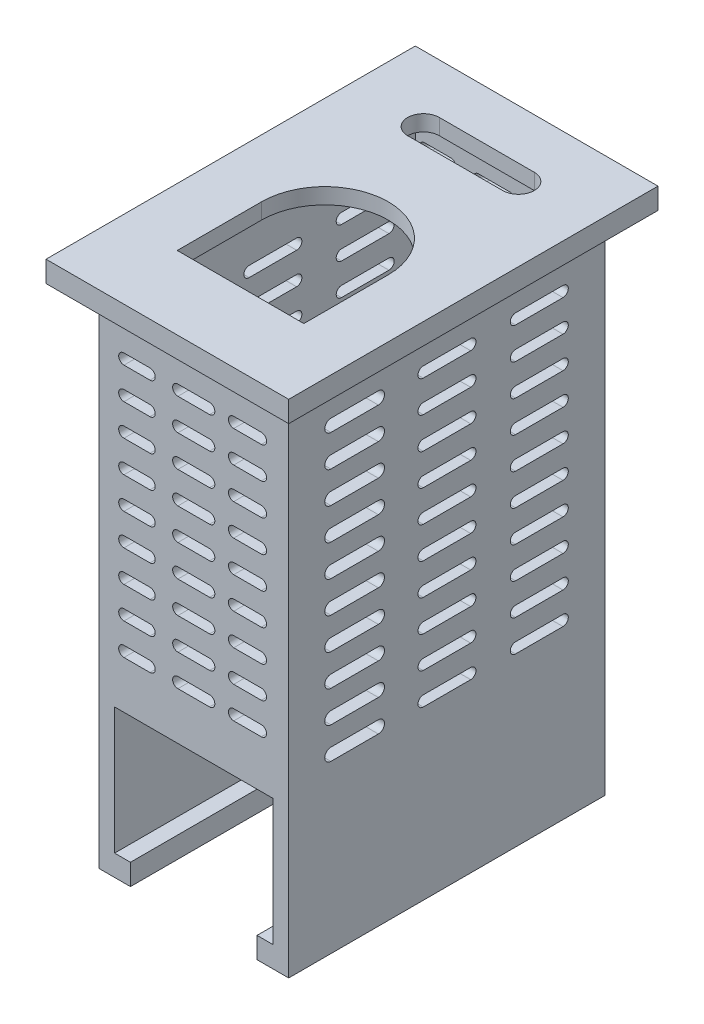
SolidWorks part; units mm, degrees
ref_plane "Front Plane" through (0, 0, 0) normal (0, 0, 1) x (1, 0, 0)
ref_plane "Top Plane" through (0, 0, 0) normal (0, 1, 0) x (1, 0, 0)
ref_plane "Right Plane" through (0, 0, 0) normal (1, 0, 0) x (0, 0, -1)
sketch "Sketch1" plane through (0, 0, 0) normal (0, 0, 1) x (1, 0, 0)
  line L0 (-29.7369, -3.7818) -> (-29.7369, -31.9754) construction
  line L1 (-37.2369, -25.1367) -> (-37.2369, -13.1367)
  line L2 (-38.7369, -29.1367) -> (-20.7369, -29.1367)
  line L3 (-29.7369, -29.1367) -> (-29.7369, -27.1367)
  line L4 (-38.7369, -27.1367) -> (-20.7369, -27.1367)
  line L5 (-20.7369, -29.1367) -> (-20.7369, -27.1367)
  line L6 (-35.7369, -27.1367) -> (-23.7369, -27.1367)
  line L7 (-29.7369, -27.1367) -> (-29.7369, -25.1367)
  line L8 (-35.7369, -25.1367) -> (-23.7369, -25.1367)
  line L9 (-23.7369, -27.1367) -> (-23.7369, -25.1367)
  line L10 (-37.2369, -25.1367) -> (-22.2369, -25.1367)
  line L11 (-29.7369, -25.1367) -> (-29.7369, -13.1367)
  line L12 (-37.2369, -13.1367) -> (-22.2369, -13.1367)
  line L13 (-22.2369, -25.1367) -> (-22.2369, -13.1367)
  line L14 (-35.7369, -27.1367) -> (-35.7369, -25.1367)
  line L15 (-38.7369, -29.1367) -> (-38.7369, -27.1367)
  line L16 (-38.7369, -27.1367) -> (-20.7369, -27.1367)
  line L17 (-38.7369, -27.1367) -> (-38.7369, 20.8633)
  line L18 (-20.7369, -27.1367) -> (-20.7369, 20.8633)
  line L19 (-38.7369, 20.8633) -> (-20.7369, 20.8633)
  line L21 (-41.2369, 20.8633) -> (-18.2369, 20.8633)
  line L22 (-41.2369, 20.8633) -> (-41.2369, 22.8633)
  line L23 (-41.2369, 22.8633) -> (-18.2369, 22.8633)
  line L24 (-18.2369, 20.8633) -> (-18.2369, 22.8633)
  point P24 (0, 0)
  dimension "D1" = 2
  dimension "D2" = 2
  dimension "D3" = 16
  dimension "D4" = 9
  dimension "D5" = 6
  dimension "D6" = 7.5
  dimension "D7" = 50
  dimension "D8" = 2
  dimension "D9" = 2.5
  dimension "D10" = 2.5
extrude "Boss-Extrude1" add sketch "Sketch1" along normal blind 30 contours L19 L17 L4 L14 L10 L1 L12 L13 L9 L18 | L21 L24 L23 L22 L19 region at (-29.7369, 2.0633, 0) region at (-29.7369, 21.8633, 0)
shell "Shell5" thickness 1.5 removed face at (-29.7369, -13.1367, 15)
sketch "Sketch2" plane through (-20.7369, 0, 0) normal (1, 0, 0) x (0, 0, -1)
  line L0 (-30, 22.8633) -> (0, 22.8633) construction
  line L1 (-26, 16.2284) -> (0, 16.2284) construction
  line L2 (0, -27.1367) -> (0, 20.8633) construction
  line L3 (-26, 16.2284) -> (-21.5035, 16.2284) construction
  line L4 (-26, 16.8123) -> (-21.5035, 16.8123)
  line L5 (-26, 15.6445) -> (-21.5035, 15.6445)
  line L6 (-17.2482, 16.2284) -> (-12.7518, 16.2284) construction
  line L7 (-17.2482, 16.7284) -> (-12.7518, 16.7284)
  line L8 (-17.2482, 15.7284) -> (-12.7518, 15.7284)
  line L9 (-8.4965, 16.2119) -> (-4, 16.2119) construction
  line L10 (-8.4965, 16.7119) -> (-4, 16.7119)
  line L11 (-8.4965, 15.7119) -> (-4, 15.7119)
  line L12 (-15, 22.8633) -> (-15, -27.1367) construction
  line L13 (-30, -27.1367) -> (0, -27.1367) construction
  line L14 (-30, -27.1367) -> (-30, 20.8633) construction
  line L15 (-26, 13.2284) -> (-21.5035, 13.2284) construction
  line L16 (-26, 13.8123) -> (-21.5035, 13.8123)
  line L17 (-26, 12.6445) -> (-21.5035, 12.6445)
  line L18 (-17.2482, 13.2284) -> (-12.7518, 13.2284) construction
  line L19 (-17.2482, 13.7284) -> (-12.7518, 13.7284)
  line L20 (-17.2482, 12.7284) -> (-12.7518, 12.7284)
  line L21 (-8.4965, 13.2119) -> (-4, 13.2119) construction
  line L22 (-8.4965, 13.7119) -> (-4, 13.7119)
  line L23 (-8.4965, 12.7119) -> (-4, 12.7119)
  line L24 (-26, 10.2284) -> (-21.5035, 10.2284) construction
  line L25 (-26, 10.8123) -> (-21.5035, 10.8123)
  line L26 (-26, 9.6445) -> (-21.5035, 9.6445)
  line L27 (-17.2482, 10.2284) -> (-12.7518, 10.2284) construction
  line L28 (-17.2482, 10.7284) -> (-12.7518, 10.7284)
  line L29 (-17.2482, 9.7284) -> (-12.7518, 9.7284)
  line L30 (-8.4965, 10.2119) -> (-4, 10.2119) construction
  line L31 (-8.4965, 10.7119) -> (-4, 10.7119)
  line L32 (-8.4965, 9.7119) -> (-4, 9.7119)
  line L33 (-26, 7.2284) -> (-21.5035, 7.2284) construction
  line L34 (-26, 7.8123) -> (-21.5035, 7.8123)
  line L35 (-26, 6.6445) -> (-21.5035, 6.6445)
  line L36 (-17.2482, 7.2284) -> (-12.7518, 7.2284) construction
  line L37 (-17.2482, 7.7284) -> (-12.7518, 7.7284)
  line L38 (-17.2482, 6.7284) -> (-12.7518, 6.7284)
  line L39 (-8.4965, 7.2119) -> (-4, 7.2119) construction
  line L40 (-8.4965, 7.7119) -> (-4, 7.7119)
  line L41 (-8.4965, 6.7119) -> (-4, 6.7119)
  line L42 (-26, 4.2284) -> (-21.5035, 4.2284) construction
  line L43 (-26, 4.8123) -> (-21.5035, 4.8123)
  line L44 (-26, 3.6445) -> (-21.5035, 3.6445)
  line L45 (-17.2482, 4.2284) -> (-12.7518, 4.2284) construction
  line L46 (-17.2482, 4.7284) -> (-12.7518, 4.7284)
  line L47 (-17.2482, 3.7284) -> (-12.7518, 3.7284)
  line L48 (-8.4965, 4.2119) -> (-4, 4.2119) construction
  line L49 (-8.4965, 4.7119) -> (-4, 4.7119)
  line L50 (-8.4965, 3.7119) -> (-4, 3.7119)
  line L51 (-26, 1.2284) -> (-21.5035, 1.2284) construction
  line L52 (-26, 1.8123) -> (-21.5035, 1.8123)
  line L53 (-26, 0.6445) -> (-21.5035, 0.6445)
  line L54 (-17.2482, 1.2284) -> (-12.7518, 1.2284) construction
  line L55 (-17.2482, 1.7284) -> (-12.7518, 1.7284)
  line L56 (-17.2482, 0.7284) -> (-12.7518, 0.7284)
  line L57 (-8.4965, 1.2119) -> (-4, 1.2119) construction
  line L58 (-8.4965, 1.7119) -> (-4, 1.7119)
  line L59 (-8.4965, 0.7119) -> (-4, 0.7119)
  line L60 (-26, -1.7716) -> (-21.5035, -1.7716) construction
  line L61 (-26, -1.1877) -> (-21.5035, -1.1877)
  line L62 (-26, -2.3555) -> (-21.5035, -2.3555)
  line L63 (-17.2482, -1.7716) -> (-12.7518, -1.7716) construction
  line L64 (-17.2482, -1.2716) -> (-12.7518, -1.2716)
  line L65 (-17.2482, -2.2716) -> (-12.7518, -2.2716)
  line L66 (-8.4965, -1.7881) -> (-4, -1.7881) construction
  line L67 (-8.4965, -1.2881) -> (-4, -1.2881)
  line L68 (-8.4965, -2.2881) -> (-4, -2.2881)
  line L69 (-26, -4.7716) -> (-21.5035, -4.7716) construction
  line L70 (-26, -4.1877) -> (-21.5035, -4.1877)
  line L71 (-26, -5.3555) -> (-21.5035, -5.3555)
  line L72 (-17.2482, -4.7716) -> (-12.7518, -4.7716) construction
  line L73 (-17.2482, -4.2716) -> (-12.7518, -4.2716)
  line L74 (-17.2482, -5.2716) -> (-12.7518, -5.2716)
  line L75 (-8.4965, -4.7881) -> (-4, -4.7881) construction
  line L76 (-8.4965, -4.2881) -> (-4, -4.2881)
  line L77 (-8.4965, -5.2881) -> (-4, -5.2881)
  line L78 (-26, -7.7716) -> (-21.5035, -7.7716) construction
  line L79 (-26, -7.1877) -> (-21.5035, -7.1877)
  line L80 (-26, -8.3555) -> (-21.5035, -8.3555)
  line L81 (-17.2482, -7.7716) -> (-12.7518, -7.7716) construction
  line L82 (-17.2482, -7.2716) -> (-12.7518, -7.2716)
  line L83 (-17.2482, -8.2716) -> (-12.7518, -8.2716)
  line L84 (-8.4965, -7.7881) -> (-4, -7.7881) construction
  line L85 (-8.4965, -7.2881) -> (-4, -7.2881)
  line L86 (-8.4965, -8.2881) -> (-4, -8.2881)
  line L87 (-26, -10.7716) -> (-21.5035, -10.7716) construction
  line L88 (-26, -10.1877) -> (-21.5035, -10.1877)
  line L89 (-26, -11.3555) -> (-21.5035, -11.3555)
  line L90 (-17.2482, -10.7716) -> (-12.7518, -10.7716) construction
  line L91 (-17.2482, -10.2716) -> (-12.7518, -10.2716)
  line L92 (-17.2482, -11.2716) -> (-12.7518, -11.2716)
  line L93 (-8.4965, -10.7881) -> (-4, -10.7881) construction
  line L94 (-8.4965, -10.2881) -> (-4, -10.2881)
  line L95 (-8.4965, -11.2881) -> (-4, -11.2881)
  arc A0 (-26, 16.8123) -> (-26, 15.6445) centre (-26, 16.2284) ccw
  arc A1 (-21.5035, 15.6445) -> (-21.5035, 16.8123) centre (-21.5035, 16.2284) ccw
  arc A2 (-17.2482, 16.7284) -> (-17.2482, 15.7284) centre (-17.2482, 16.2284) ccw
  arc A3 (-12.7518, 15.7284) -> (-12.7518, 16.7284) centre (-12.7518, 16.2284) ccw
  arc A4 (-8.4965, 16.7119) -> (-8.4965, 15.7119) centre (-8.4965, 16.2119) ccw
  arc A5 (-4, 15.7119) -> (-4, 16.7119) centre (-4, 16.2119) ccw
  arc A6 (-26, 13.8123) -> (-26, 12.6445) centre (-26, 13.2284) ccw
  arc A7 (-21.5035, 12.6445) -> (-21.5035, 13.8123) centre (-21.5035, 13.2284) ccw
  arc A8 (-17.2482, 13.7284) -> (-17.2482, 12.7284) centre (-17.2482, 13.2284) ccw
  arc A9 (-12.7518, 12.7284) -> (-12.7518, 13.7284) centre (-12.7518, 13.2284) ccw
  arc A10 (-8.4965, 13.7119) -> (-8.4965, 12.7119) centre (-8.4965, 13.2119) ccw
  arc A11 (-4, 12.7119) -> (-4, 13.7119) centre (-4, 13.2119) ccw
  arc A12 (-26, 10.8123) -> (-26, 9.6445) centre (-26, 10.2284) ccw
  arc A13 (-21.5035, 9.6445) -> (-21.5035, 10.8123) centre (-21.5035, 10.2284) ccw
  arc A14 (-17.2482, 10.7284) -> (-17.2482, 9.7284) centre (-17.2482, 10.2284) ccw
  arc A15 (-12.7518, 9.7284) -> (-12.7518, 10.7284) centre (-12.7518, 10.2284) ccw
  arc A16 (-8.4965, 10.7119) -> (-8.4965, 9.7119) centre (-8.4965, 10.2119) ccw
  arc A17 (-4, 9.7119) -> (-4, 10.7119) centre (-4, 10.2119) ccw
  arc A18 (-26, 7.8123) -> (-26, 6.6445) centre (-26, 7.2284) ccw
  arc A19 (-21.5035, 6.6445) -> (-21.5035, 7.8123) centre (-21.5035, 7.2284) ccw
  arc A20 (-17.2482, 7.7284) -> (-17.2482, 6.7284) centre (-17.2482, 7.2284) ccw
  arc A21 (-12.7518, 6.7284) -> (-12.7518, 7.7284) centre (-12.7518, 7.2284) ccw
  arc A22 (-8.4965, 7.7119) -> (-8.4965, 6.7119) centre (-8.4965, 7.2119) ccw
  arc A23 (-4, 6.7119) -> (-4, 7.7119) centre (-4, 7.2119) ccw
  arc A24 (-26, 4.8123) -> (-26, 3.6445) centre (-26, 4.2284) ccw
  arc A25 (-21.5035, 3.6445) -> (-21.5035, 4.8123) centre (-21.5035, 4.2284) ccw
  arc A26 (-17.2482, 4.7284) -> (-17.2482, 3.7284) centre (-17.2482, 4.2284) ccw
  arc A27 (-12.7518, 3.7284) -> (-12.7518, 4.7284) centre (-12.7518, 4.2284) ccw
  arc A28 (-8.4965, 4.7119) -> (-8.4965, 3.7119) centre (-8.4965, 4.2119) ccw
  arc A29 (-4, 3.7119) -> (-4, 4.7119) centre (-4, 4.2119) ccw
  arc A30 (-26, 1.8123) -> (-26, 0.6445) centre (-26, 1.2284) ccw
  arc A31 (-21.5035, 0.6445) -> (-21.5035, 1.8123) centre (-21.5035, 1.2284) ccw
  arc A32 (-17.2482, 1.7284) -> (-17.2482, 0.7284) centre (-17.2482, 1.2284) ccw
  arc A33 (-12.7518, 0.7284) -> (-12.7518, 1.7284) centre (-12.7518, 1.2284) ccw
  arc A34 (-8.4965, 1.7119) -> (-8.4965, 0.7119) centre (-8.4965, 1.2119) ccw
  arc A35 (-4, 0.7119) -> (-4, 1.7119) centre (-4, 1.2119) ccw
  arc A36 (-26, -1.1877) -> (-26, -2.3555) centre (-26, -1.7716) ccw
  arc A37 (-21.5035, -2.3555) -> (-21.5035, -1.1877) centre (-21.5035, -1.7716) ccw
  arc A38 (-17.2482, -1.2716) -> (-17.2482, -2.2716) centre (-17.2482, -1.7716) ccw
  arc A39 (-12.7518, -2.2716) -> (-12.7518, -1.2716) centre (-12.7518, -1.7716) ccw
  arc A40 (-8.4965, -1.2881) -> (-8.4965, -2.2881) centre (-8.4965, -1.7881) ccw
  arc A41 (-4, -2.2881) -> (-4, -1.2881) centre (-4, -1.7881) ccw
  arc A42 (-26, -4.1877) -> (-26, -5.3555) centre (-26, -4.7716) ccw
  arc A43 (-21.5035, -5.3555) -> (-21.5035, -4.1877) centre (-21.5035, -4.7716) ccw
  arc A44 (-17.2482, -4.2716) -> (-17.2482, -5.2716) centre (-17.2482, -4.7716) ccw
  arc A45 (-12.7518, -5.2716) -> (-12.7518, -4.2716) centre (-12.7518, -4.7716) ccw
  arc A46 (-8.4965, -4.2881) -> (-8.4965, -5.2881) centre (-8.4965, -4.7881) ccw
  arc A47 (-4, -5.2881) -> (-4, -4.2881) centre (-4, -4.7881) ccw
  arc A48 (-26, -7.1877) -> (-26, -8.3555) centre (-26, -7.7716) ccw
  arc A49 (-21.5035, -8.3555) -> (-21.5035, -7.1877) centre (-21.5035, -7.7716) ccw
  arc A50 (-17.2482, -7.2716) -> (-17.2482, -8.2716) centre (-17.2482, -7.7716) ccw
  arc A51 (-12.7518, -8.2716) -> (-12.7518, -7.2716) centre (-12.7518, -7.7716) ccw
  arc A52 (-8.4965, -7.2881) -> (-8.4965, -8.2881) centre (-8.4965, -7.7881) ccw
  arc A53 (-4, -8.2881) -> (-4, -7.2881) centre (-4, -7.7881) ccw
  arc A54 (-26, -10.1877) -> (-26, -11.3555) centre (-26, -10.7716) ccw
  arc A55 (-21.5035, -11.3555) -> (-21.5035, -10.1877) centre (-21.5035, -10.7716) ccw
  arc A56 (-17.2482, -10.2716) -> (-17.2482, -11.2716) centre (-17.2482, -10.7716) ccw
  arc A57 (-12.7518, -11.2716) -> (-12.7518, -10.2716) centre (-12.7518, -10.7716) ccw
  arc A58 (-8.4965, -10.2881) -> (-8.4965, -11.2881) centre (-8.4965, -10.7881) ccw
  arc A59 (-4, -11.2881) -> (-4, -10.2881) centre (-4, -10.7881) ccw
  point P0 (-26, 16.2284)
  point P7 (-23.7518, 16.2284)
  point P14 (-15, 16.2284)
  point P21 (-6.2482, 16.2119)
  point P35 (-26, 13.2284)
  point P37 (-23.7518, 13.2284)
  point P44 (-15, 13.2284)
  point P51 (-6.2482, 13.2119)
  point P57 (-26, 10.2284)
  point P59 (-23.7518, 10.2284)
  point P66 (-15, 10.2284)
  point P73 (-6.2482, 10.2119)
  point P79 (-26, 7.2284)
  point P81 (-23.7518, 7.2284)
  point P88 (-15, 7.2284)
  point P95 (-6.2482, 7.2119)
  point P101 (-26, 4.2284)
  point P103 (-23.7518, 4.2284)
  point P110 (-15, 4.2284)
  point P117 (-6.2482, 4.2119)
  point P123 (-26, 1.2284)
  point P125 (-23.7518, 1.2284)
  point P132 (-15, 1.2284)
  point P139 (-6.2482, 1.2119)
  point P145 (-26, -1.7716)
  point P147 (-23.7518, -1.7716)
  point P154 (-15, -1.7716)
  point P161 (-6.2482, -1.7881)
  point P167 (-26, -4.7716)
  point P169 (-23.7518, -4.7716)
  point P176 (-15, -4.7716)
  point P183 (-6.2482, -4.7881)
  point P189 (-26, -7.7716)
  point P191 (-23.7518, -7.7716)
  point P198 (-15, -7.7716)
  point P205 (-6.2482, -7.7881)
  point P211 (-26, -10.7716)
  point P213 (-23.7518, -10.7716)
  point P220 (-15, -10.7716)
  point P227 (-6.2482, -10.7881)
  dimension "D2" = 4
  dimension "D1" = 6.6349
  dimension "D3" = 4
  dimension "D4" = 10
extrude "Cut-Extrude1" cut sketch "Sketch2" against normal through all
sketch "Sketch3" plane through (0, 0, 0) normal (0, 0, -1) x (-1, 0, 0)
  line L0 (29.7369, 22.8633) -> (29.7369, -13.1367) construction
  line L1 (41.2369, 22.8633) -> (18.2369, 22.8633) construction
  line L2 (37.2369, -13.1367) -> (22.2369, -13.1367) construction
  line L3 (23.3338, 18.8633) -> (25.9476, 18.8633) construction
  line L4 (23.3338, 19.3633) -> (25.9476, 19.3633)
  line L5 (23.3338, 18.3633) -> (25.9476, 18.3633)
  line L6 (28.2369, 18.8633) -> (31.2369, 18.8633) construction
  line L7 (28.2369, 19.3633) -> (31.2369, 19.3633)
  line L8 (28.2369, 18.3633) -> (31.2369, 18.3633)
  line L9 (33.8847, 18.8633) -> (36.3499, 18.8633) construction
  line L10 (33.8847, 19.3633) -> (36.3499, 19.3633)
  line L11 (33.8847, 18.3633) -> (36.3499, 18.3633)
  line L12 (23.3338, 15.8633) -> (25.9476, 15.8633) construction
  line L13 (23.3338, 16.3633) -> (25.9476, 16.3633)
  line L14 (23.3338, 15.3633) -> (25.9476, 15.3633)
  line L15 (28.2369, 15.8633) -> (31.2369, 15.8633) construction
  line L16 (28.2369, 16.3633) -> (31.2369, 16.3633)
  line L17 (28.2369, 15.3633) -> (31.2369, 15.3633)
  line L18 (33.8847, 15.8633) -> (36.3499, 15.8633) construction
  line L19 (33.8847, 16.3633) -> (36.3499, 16.3633)
  line L20 (33.8847, 15.3633) -> (36.3499, 15.3633)
  line L21 (23.3338, 12.8633) -> (25.9476, 12.8633) construction
  line L22 (23.3338, 13.3633) -> (25.9476, 13.3633)
  line L23 (23.3338, 12.3633) -> (25.9476, 12.3633)
  line L24 (28.2369, 12.8633) -> (31.2369, 12.8633) construction
  line L25 (28.2369, 13.3633) -> (31.2369, 13.3633)
  line L26 (28.2369, 12.3633) -> (31.2369, 12.3633)
  line L27 (33.8847, 12.8633) -> (36.3499, 12.8633) construction
  line L28 (33.8847, 13.3633) -> (36.3499, 13.3633)
  line L29 (33.8847, 12.3633) -> (36.3499, 12.3633)
  line L30 (23.3338, 9.8633) -> (25.9476, 9.8633) construction
  line L31 (23.3338, 10.3633) -> (25.9476, 10.3633)
  line L32 (23.3338, 9.3633) -> (25.9476, 9.3633)
  line L33 (28.2369, 9.8633) -> (31.2369, 9.8633) construction
  line L34 (28.2369, 10.3633) -> (31.2369, 10.3633)
  line L35 (28.2369, 9.3633) -> (31.2369, 9.3633)
  line L36 (33.8847, 9.8633) -> (36.3499, 9.8633) construction
  line L37 (33.8847, 10.3633) -> (36.3499, 10.3633)
  line L38 (33.8847, 9.3633) -> (36.3499, 9.3633)
  line L39 (23.3338, 6.8633) -> (25.9476, 6.8633) construction
  line L40 (23.3338, 7.3633) -> (25.9476, 7.3633)
  line L41 (23.3338, 6.3633) -> (25.9476, 6.3633)
  line L42 (28.2369, 6.8633) -> (31.2369, 6.8633) construction
  line L43 (28.2369, 7.3633) -> (31.2369, 7.3633)
  line L44 (28.2369, 6.3633) -> (31.2369, 6.3633)
  line L45 (33.8847, 6.8633) -> (36.3499, 6.8633) construction
  line L46 (33.8847, 7.3633) -> (36.3499, 7.3633)
  line L47 (33.8847, 6.3633) -> (36.3499, 6.3633)
  line L48 (23.3338, 3.8633) -> (25.9476, 3.8633) construction
  line L49 (23.3338, 4.3633) -> (25.9476, 4.3633)
  line L50 (23.3338, 3.3633) -> (25.9476, 3.3633)
  line L51 (28.2369, 3.8633) -> (31.2369, 3.8633) construction
  line L52 (28.2369, 4.3633) -> (31.2369, 4.3633)
  line L53 (28.2369, 3.3633) -> (31.2369, 3.3633)
  line L54 (33.8847, 3.8633) -> (36.3499, 3.8633) construction
  line L55 (33.8847, 4.3633) -> (36.3499, 4.3633)
  line L56 (33.8847, 3.3633) -> (36.3499, 3.3633)
  line L57 (23.3338, 0.8633) -> (25.9476, 0.8633) construction
  line L58 (23.3338, 1.3633) -> (25.9476, 1.3633)
  line L59 (23.3338, 0.3633) -> (25.9476, 0.3633)
  line L60 (28.2369, 0.8633) -> (31.2369, 0.8633) construction
  line L61 (28.2369, 1.3633) -> (31.2369, 1.3633)
  line L62 (28.2369, 0.3633) -> (31.2369, 0.3633)
  line L63 (33.8847, 0.8633) -> (36.3499, 0.8633) construction
  line L64 (33.8847, 1.3633) -> (36.3499, 1.3633)
  line L65 (33.8847, 0.3633) -> (36.3499, 0.3633)
  line L66 (23.3338, -2.1367) -> (25.9476, -2.1367) construction
  line L67 (23.3338, -1.6367) -> (25.9476, -1.6367)
  line L68 (23.3338, -2.6367) -> (25.9476, -2.6367)
  line L69 (28.2369, -2.1367) -> (31.2369, -2.1367) construction
  line L70 (28.2369, -1.6367) -> (31.2369, -1.6367)
  line L71 (28.2369, -2.6367) -> (31.2369, -2.6367)
  line L72 (33.8847, -2.1367) -> (36.3499, -2.1367) construction
  line L73 (33.8847, -1.6367) -> (36.3499, -1.6367)
  line L74 (33.8847, -2.6367) -> (36.3499, -2.6367)
  line L75 (23.3338, -5.1367) -> (25.9476, -5.1367) construction
  line L76 (23.3338, -4.6367) -> (25.9476, -4.6367)
  line L77 (23.3338, -5.6367) -> (25.9476, -5.6367)
  line L78 (28.2369, -5.1367) -> (31.2369, -5.1367) construction
  line L79 (28.2369, -4.6367) -> (31.2369, -4.6367)
  line L80 (28.2369, -5.6367) -> (31.2369, -5.6367)
  line L81 (33.8847, -5.1367) -> (36.3499, -5.1367) construction
  line L82 (33.8847, -4.6367) -> (36.3499, -4.6367)
  line L83 (33.8847, -5.6367) -> (36.3499, -5.6367)
  line L84 (23.3338, -8.1367) -> (25.9476, -8.1367) construction
  line L85 (23.3338, -7.6367) -> (25.9476, -7.6367)
  line L86 (23.3338, -8.6367) -> (25.9476, -8.6367)
  line L87 (28.2369, -8.1367) -> (31.2369, -8.1367) construction
  line L88 (28.2369, -7.6367) -> (31.2369, -7.6367)
  line L89 (28.2369, -8.6367) -> (31.2369, -8.6367)
  line L90 (33.8847, -8.1367) -> (36.3499, -8.1367) construction
  line L91 (33.8847, -7.6367) -> (36.3499, -7.6367)
  line L92 (33.8847, -8.6367) -> (36.3499, -8.6367)
  arc A0 (23.3338, 19.3633) -> (23.3338, 18.3633) centre (23.3338, 18.8633) ccw
  arc A1 (25.9476, 18.3633) -> (25.9476, 19.3633) centre (25.9476, 18.8633) ccw
  arc A2 (28.2369, 19.3633) -> (28.2369, 18.3633) centre (28.2369, 18.8633) ccw
  arc A3 (31.2369, 18.3633) -> (31.2369, 19.3633) centre (31.2369, 18.8633) ccw
  arc A4 (33.8847, 19.3633) -> (33.8847, 18.3633) centre (33.8847, 18.8633) ccw
  arc A5 (36.3499, 18.3633) -> (36.3499, 19.3633) centre (36.3499, 18.8633) ccw
  arc A6 (23.3338, 16.3633) -> (23.3338, 15.3633) centre (23.3338, 15.8633) ccw
  arc A7 (25.9476, 15.3633) -> (25.9476, 16.3633) centre (25.9476, 15.8633) ccw
  arc A8 (28.2369, 16.3633) -> (28.2369, 15.3633) centre (28.2369, 15.8633) ccw
  arc A9 (31.2369, 15.3633) -> (31.2369, 16.3633) centre (31.2369, 15.8633) ccw
  arc A10 (33.8847, 16.3633) -> (33.8847, 15.3633) centre (33.8847, 15.8633) ccw
  arc A11 (36.3499, 15.3633) -> (36.3499, 16.3633) centre (36.3499, 15.8633) ccw
  arc A12 (23.3338, 13.3633) -> (23.3338, 12.3633) centre (23.3338, 12.8633) ccw
  arc A13 (25.9476, 12.3633) -> (25.9476, 13.3633) centre (25.9476, 12.8633) ccw
  arc A14 (28.2369, 13.3633) -> (28.2369, 12.3633) centre (28.2369, 12.8633) ccw
  arc A15 (31.2369, 12.3633) -> (31.2369, 13.3633) centre (31.2369, 12.8633) ccw
  arc A16 (33.8847, 13.3633) -> (33.8847, 12.3633) centre (33.8847, 12.8633) ccw
  arc A17 (36.3499, 12.3633) -> (36.3499, 13.3633) centre (36.3499, 12.8633) ccw
  arc A18 (23.3338, 10.3633) -> (23.3338, 9.3633) centre (23.3338, 9.8633) ccw
  arc A19 (25.9476, 9.3633) -> (25.9476, 10.3633) centre (25.9476, 9.8633) ccw
  arc A20 (28.2369, 10.3633) -> (28.2369, 9.3633) centre (28.2369, 9.8633) ccw
  arc A21 (31.2369, 9.3633) -> (31.2369, 10.3633) centre (31.2369, 9.8633) ccw
  arc A22 (33.8847, 10.3633) -> (33.8847, 9.3633) centre (33.8847, 9.8633) ccw
  arc A23 (36.3499, 9.3633) -> (36.3499, 10.3633) centre (36.3499, 9.8633) ccw
  arc A24 (23.3338, 7.3633) -> (23.3338, 6.3633) centre (23.3338, 6.8633) ccw
  arc A25 (25.9476, 6.3633) -> (25.9476, 7.3633) centre (25.9476, 6.8633) ccw
  arc A26 (28.2369, 7.3633) -> (28.2369, 6.3633) centre (28.2369, 6.8633) ccw
  arc A27 (31.2369, 6.3633) -> (31.2369, 7.3633) centre (31.2369, 6.8633) ccw
  arc A28 (33.8847, 7.3633) -> (33.8847, 6.3633) centre (33.8847, 6.8633) ccw
  arc A29 (36.3499, 6.3633) -> (36.3499, 7.3633) centre (36.3499, 6.8633) ccw
  arc A30 (23.3338, 4.3633) -> (23.3338, 3.3633) centre (23.3338, 3.8633) ccw
  arc A31 (25.9476, 3.3633) -> (25.9476, 4.3633) centre (25.9476, 3.8633) ccw
  arc A32 (28.2369, 4.3633) -> (28.2369, 3.3633) centre (28.2369, 3.8633) ccw
  arc A33 (31.2369, 3.3633) -> (31.2369, 4.3633) centre (31.2369, 3.8633) ccw
  arc A34 (33.8847, 4.3633) -> (33.8847, 3.3633) centre (33.8847, 3.8633) ccw
  arc A35 (36.3499, 3.3633) -> (36.3499, 4.3633) centre (36.3499, 3.8633) ccw
  arc A36 (23.3338, 1.3633) -> (23.3338, 0.3633) centre (23.3338, 0.8633) ccw
  arc A37 (25.9476, 0.3633) -> (25.9476, 1.3633) centre (25.9476, 0.8633) ccw
  arc A38 (28.2369, 1.3633) -> (28.2369, 0.3633) centre (28.2369, 0.8633) ccw
  arc A39 (31.2369, 0.3633) -> (31.2369, 1.3633) centre (31.2369, 0.8633) ccw
  arc A40 (33.8847, 1.3633) -> (33.8847, 0.3633) centre (33.8847, 0.8633) ccw
  arc A41 (36.3499, 0.3633) -> (36.3499, 1.3633) centre (36.3499, 0.8633) ccw
  arc A42 (23.3338, -1.6367) -> (23.3338, -2.6367) centre (23.3338, -2.1367) ccw
  arc A43 (25.9476, -2.6367) -> (25.9476, -1.6367) centre (25.9476, -2.1367) ccw
  arc A44 (28.2369, -1.6367) -> (28.2369, -2.6367) centre (28.2369, -2.1367) ccw
  arc A45 (31.2369, -2.6367) -> (31.2369, -1.6367) centre (31.2369, -2.1367) ccw
  arc A46 (33.8847, -1.6367) -> (33.8847, -2.6367) centre (33.8847, -2.1367) ccw
  arc A47 (36.3499, -2.6367) -> (36.3499, -1.6367) centre (36.3499, -2.1367) ccw
  arc A48 (23.3338, -4.6367) -> (23.3338, -5.6367) centre (23.3338, -5.1367) ccw
  arc A49 (25.9476, -5.6367) -> (25.9476, -4.6367) centre (25.9476, -5.1367) ccw
  arc A50 (28.2369, -4.6367) -> (28.2369, -5.6367) centre (28.2369, -5.1367) ccw
  arc A51 (31.2369, -5.6367) -> (31.2369, -4.6367) centre (31.2369, -5.1367) ccw
  arc A52 (33.8847, -4.6367) -> (33.8847, -5.6367) centre (33.8847, -5.1367) ccw
  arc A53 (36.3499, -5.6367) -> (36.3499, -4.6367) centre (36.3499, -5.1367) ccw
  arc A54 (23.3338, -7.6367) -> (23.3338, -8.6367) centre (23.3338, -8.1367) ccw
  arc A55 (25.9476, -8.6367) -> (25.9476, -7.6367) centre (25.9476, -8.1367) ccw
  arc A56 (28.2369, -7.6367) -> (28.2369, -8.6367) centre (28.2369, -8.1367) ccw
  arc A57 (31.2369, -8.6367) -> (31.2369, -7.6367) centre (31.2369, -8.1367) ccw
  arc A58 (33.8847, -7.6367) -> (33.8847, -8.6367) centre (33.8847, -8.1367) ccw
  arc A59 (36.3499, -8.6367) -> (36.3499, -7.6367) centre (36.3499, -8.1367) ccw
  point P6 (23.3338, 18.8633)
  point P9 (24.6407, 18.8633)
  point P14 (29.7369, 18.8633)
  point P21 (35.1173, 18.8633)
  point P28 (23.3338, 15.8633)
  point P29 (0, 0)
  point P32 (24.6407, 15.8633)
  point P37 (29.7369, 15.8633)
  point P44 (35.1173, 15.8633)
  point P51 (23.3338, 12.8633)
  point P54 (24.6407, 12.8633)
  point P59 (29.7369, 12.8633)
  point P66 (35.1173, 12.8633)
  point P73 (23.3338, 9.8633)
  point P76 (24.6407, 9.8633)
  point P81 (29.7369, 9.8633)
  point P88 (35.1173, 9.8633)
  point P95 (23.3338, 6.8633)
  point P98 (24.6407, 6.8633)
  point P103 (29.7369, 6.8633)
  point P110 (35.1173, 6.8633)
  point P117 (23.3338, 3.8633)
  point P120 (24.6407, 3.8633)
  point P125 (29.7369, 3.8633)
  point P132 (35.1173, 3.8633)
  point P139 (23.3338, 0.8633)
  point P142 (24.6407, 0.8633)
  point P147 (29.7369, 0.8633)
  point P154 (35.1173, 0.8633)
  point P161 (23.3338, -2.1367)
  point P164 (24.6407, -2.1367)
  point P169 (29.7369, -2.1367)
  point P176 (35.1173, -2.1367)
  point P183 (23.3338, -5.1367)
  point P186 (24.6407, -5.1367)
  point P191 (29.7369, -5.1367)
  point P198 (35.1173, -5.1367)
  point P205 (23.3338, -8.1367)
  point P208 (24.6407, -8.1367)
  point P213 (29.7369, -8.1367)
  point P220 (35.1173, -8.1367)
  point P227 (23.3338, 18.8633)
  point P228 (0, 0)
  point P229 (0, 0)
  point P230 (36.5118, 18.8633)
  point P231 (36.1159, 18.8633)
  point P232 (36.3499, 18.8633)
  dimension "D2" = 10
  dimension "D1" = 4
extrude "Cut-Extrude2" cut sketch "Sketch3" against normal through all
sketch "Sketch4" plane through (0, 22.8633, 0) normal (0, 1, 0) x (1, 0, 0)
  line L0 (-34.2338, -3.7257) -> (-25.2338, -3.7257) construction
  line L1 (-34.2338, -2.2257) -> (-25.2338, -2.2257)
  line L2 (-34.2338, -5.2257) -> (-25.2338, -5.2257)
  line L3 (-29.7369, 0) -> (-29.7369, -30) construction
  line L4 (-41.2369, 0) -> (-18.2369, 0) construction
  line L5 (-41.2369, -30) -> (-18.2369, -30) construction
  line L7 (-35.7369, -17.5662) -> (-23.7369, -17.5662)
  line L8 (-35.7369, -17.5662) -> (-35.7369, -25.5662)
  line L9 (-35.7369, -25.5662) -> (-23.7369, -25.5662)
  line L10 (-23.7369, -17.5662) -> (-23.7369, -25.5662)
  line L11 (-35.7369, -17.5662) -> (-23.7369, -25.5662) construction
  line L12 (-35.7369, -25.5662) -> (-23.7369, -17.5662) construction
  arc A0 (-34.2338, -2.2257) -> (-34.2338, -5.2257) centre (-34.2338, -3.7257) ccw
  arc A1 (-25.2338, -5.2257) -> (-25.2338, -2.2257) centre (-25.2338, -3.7257) ccw
  arc A2 (-35.7369, -17.5662) -> (-23.7369, -17.5662) centre (-29.7369, -17.5662) cw
  point P2 (-29.7338, -3.7257)
  point P13 (-29.7369, -21.5662)
  dimension "D1" = 12
  dimension "D2" = 8
extrude "Cut-Extrude4" cut sketch "Sketch4" against normal through all contours L10 L7 L8 L9 | A2 L7 | L2 A1 L1 A0 region at (-29.7338, 22.8633, 3.7257) region at (-29.7369, 22.8633, 15.0197) region at (-29.7369, 22.8633, 21.5662)
sketch "Sketch5" plane through (0, 0, 30) normal (0, 0, 1) x (1, 0, 0)
  line L1 (-41.2369, 22.8633) -> (-18.2369, 22.8633)
  line L2 (-41.2369, 22.8633) -> (-41.2369, 20.8633)
  line L3 (-41.2369, 20.8633) -> (-18.2369, 20.8633)
  line L4 (-18.2369, 22.8633) -> (-18.2369, 20.8633)
extrude "Boss-Extrude2" add sketch "Sketch5" along normal blind 2.5
sketch "Sketch6" plane through (0, 0, 0) normal (0, 0, -1) x (-1, 0, 0)
  line L1 (18.2369, 22.8633) -> (41.2369, 22.8633)
  line L2 (18.2369, 22.8633) -> (18.2369, 20.8633)
  line L3 (18.2369, 20.8633) -> (41.2369, 20.8633)
  line L4 (41.2369, 22.8633) -> (41.2369, 20.8633)
extrude "Boss-Extrude3" add sketch "Sketch6" along normal blind 2.5
